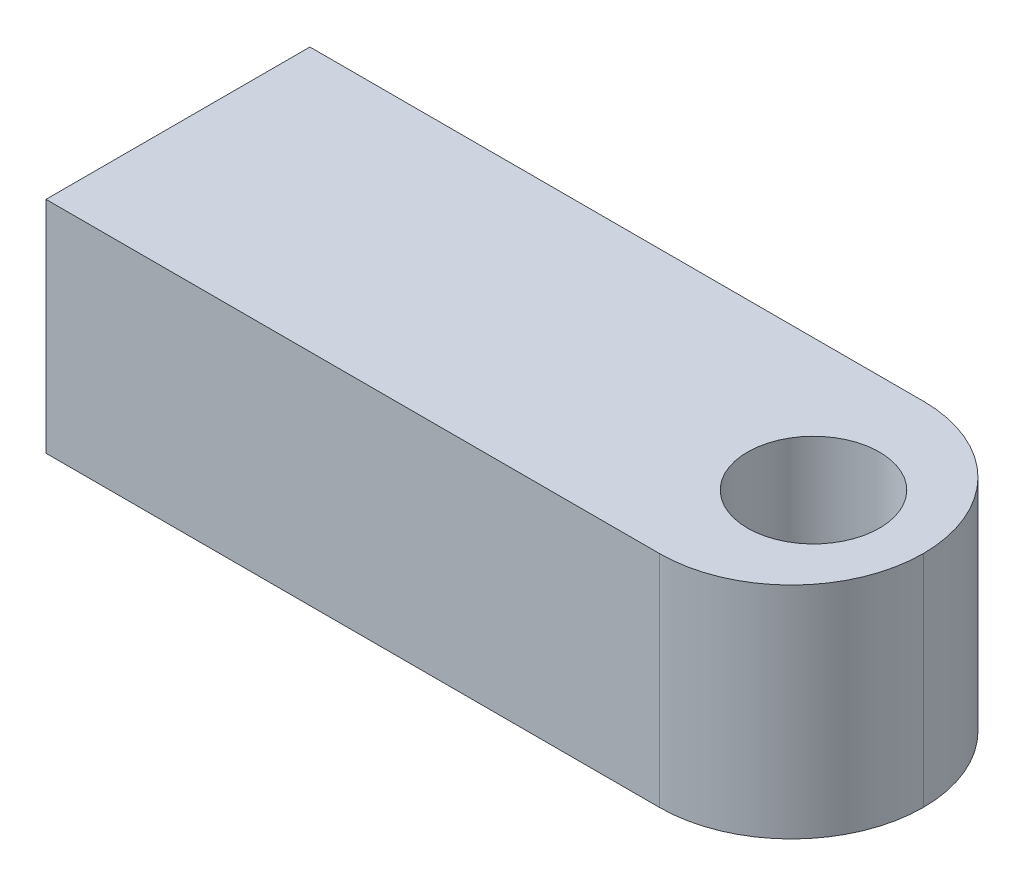
SolidWorks part; units mm, degrees
ref_plane "Front Plane" through (0, 0, 0) normal (0, 0, 1) x (1, 0, 0)
ref_plane "Top Plane" through (0, 0, 0) normal (0, 1, 0) x (1, 0, 0)
ref_plane "Right Plane" through (0, 0, 0) normal (1, 0, 0) x (0, 0, -1)
sketch "Sketch1" plane through (0, 0, 0) normal (0, 1, 0) x (1, 0, 0)
  line L0 (0, 0) -> (28.9, 0) construction
  line L2 (0, 6) -> (33.8954, 6)
  line L3 (0, 6) -> (0, -6)
  line L4 (0, -6) -> (33.8954, -6)
  line L5 (33.8954, 6) -> (33.8954, -6)
  circle A0 centre (28.9, 0) radius 3
  point P8 (0, 0)
  dimension "D2" = 6
  dimension "D1" = 28.9
  dimension "D3" = 12
extrude "Boss-Extrude1" add sketch "Sketch1" along normal blind 10 contours A0 | L2 L5 L4 L3 region at (28.9, 0, 0)
fillet "Fillet1" radius 6 2 edges at (33.8954, 5, -6) (33.8954, 5, 6)
